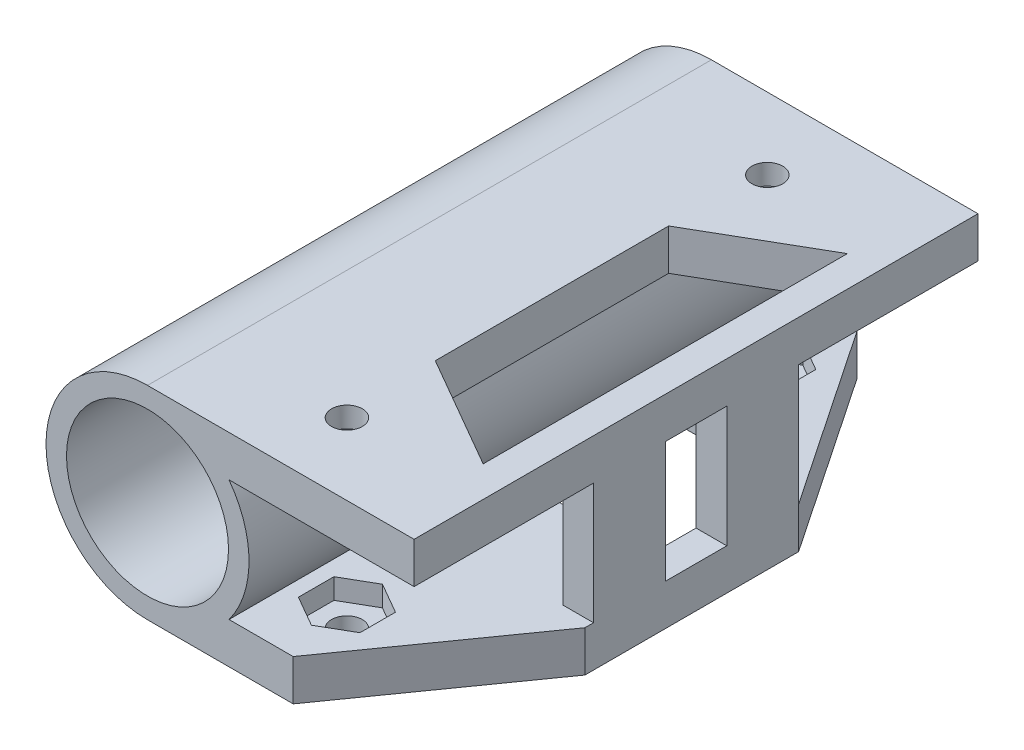
SolidWorks part; units mm, degrees
ref_plane "Спереди" through (0, 0, 0) normal (0, 0, 1) x (1, 0, 0)
ref_plane "Сверху" through (0, 0, 0) normal (0, 1, 0) x (1, 0, 0)
ref_plane "Справа" through (0, 0, 0) normal (1, 0, 0) x (0, 0, -1)
sketch "Эскиз2" plane through (0, 0, 0) normal (0, 0, 1) x (1, 0, 0)
  line L0 (0, 9.9) -> (26, 9.9)
  line L1 (26, 9.9) -> (26, 5.9)
  line L2 (26, 5.9) -> (7.9498, 5.9)
  line L3 (7.9498, -5.9) -> (26, -5.9)
  line L4 (0, -9.9) -> (26, -9.9)
  line L7 (26, -9.9) -> (26, -5.9)
  circle A0 centre (0, 0) radius 7.9
  circle A1 centre (0, 0) radius 9.9
  dimension "D2" = 15.8
  dimension "D3" = 19.8
  dimension "D1" = 4
  dimension "D4" = 26
  dimension "D5" = 4
  dimension "D6" = 26
extrude "Бобышка-Вытянуть1" add sketch "Эскиз2" against normal blind 7 and the other way blind 48 contours A1 A0 | A1 L2 L1 L0 | A1 L4 L7 L3 region at (15.6974, 8.0002, 0) region at (4.3239, 8.5935, 0) region at (15.6974, -8.0002, 0)
sketch "Эскиз3" plane through (0, 5.9, 0) normal (0, -1, 0) x (1, 0, 0)
  line L0 (26, -7) -> (7.9498, -7) construction
  line L1 (15.4498, -1.7321) -> (15.4498, 1.7321)
  line L2 (15.4498, 1.7321) -> (12.4498, 3.4641)
  line L3 (12.4498, 3.4641) -> (9.4498, 1.7321)
  line L4 (9.4498, 1.7321) -> (9.4498, -1.7321)
  line L5 (9.4498, -1.7321) -> (12.4498, -3.4641)
  line L6 (12.4498, -3.4641) -> (15.4498, -1.7321)
  line L7 (26, 20.5) -> (-7.1059, 20.5) construction
  line L8 (26, 48) -> (26, -7) construction
  line L9 (12.4498, 44.4641) -> (15.4498, 42.7321)
  line L10 (9.4498, 42.7321) -> (12.4498, 44.4641)
  line L11 (9.4498, 39.2679) -> (9.4498, 42.7321)
  line L12 (12.4498, 37.5359) -> (9.4498, 39.2679)
  line L13 (15.4498, 39.2679) -> (12.4498, 37.5359)
  line L14 (15.4498, 42.7321) -> (15.4498, 39.2679)
  circle A0 centre (12.4498, 0) radius 3 construction
  circle A1 centre (12.4498, 41) radius 3 construction
  dimension "D1" = 6
  dimension "D2" = 4.5
  dimension "D3" = 7
extrude "Вырез-Вытянуть1" cut sketch "Эскиз3" against normal blind 2
sketch "Эскиз4" plane through (0, 9.9, 0) normal (0, 1, 0) x (1, 0, 0)
  line L0 (26, -20.5) -> (0, -20.5) construction
  line L1 (26, -48) -> (26, 7) construction
  circle A0 centre (12.4498, 0) radius 1.5
  circle A1 centre (12.4498, -41) radius 1.5
  dimension "D1" = 3
extrude "Вырез-Вытянуть2" cut sketch "Эскиз4" against normal blind 28
sketch "Эскиз5" plane through (0, 9.9, 0) normal (0, 1, 0) x (1, 0, 0)
  line L0 (26, -1.0067) -> (11.9498, -9.1186)
  line L1 (26, -48) -> (26, 7) construction
  line L2 (11.9498, -9.1186) -> (11.9498, -31.8814)
  line L3 (11.9498, -31.8814) -> (26, -39.9933)
  line L4 (26, -39.9933) -> (26, -1.0067)
  line L5 (0, -48) -> (0, 7) construction
  line L6 (23, -2.7388) -> (23, -38.2612)
  line L7 (26, -48) -> (26, 7) construction
  point P4 (11.9498, -20.5)
  point P9 (0, -20.5)
  dimension "D1" = 120
  dimension "D2" = 120
  dimension "D3" = 4
  dimension "D4" = 3
extrude "Вырез-Вытянуть3" cut sketch "Эскиз5" against normal blind 10 contours L6 L0 L2 L3 region at (17.8781, 9.9, 20.5)
sketch "Эскиз7" plane through (0, 5.9, 0) normal (0, -1, 0) x (1, 0, 0)
  line L0 (23, 38.2612) -> (23, 2.7388) construction
  line L1 (23, 10.5) -> (26, 10.5)
  line L2 (23, 10.5) -> (23, 17.5)
  line L3 (23, 17.5) -> (26, 17.5)
  line L4 (26, 10.5) -> (26, 17.5)
  line L5 (26, 48) -> (26, -7) construction
  line L7 (23, 23.5) -> (26, 23.5)
  line L8 (23, 23.5) -> (23, 30.5)
  line L9 (23, 30.5) -> (26, 30.5)
  line L10 (26, 23.5) -> (26, 30.5)
  line L11 (23, 17.5) -> (26, 17.5)
  line L12 (23, 17.5) -> (23, 23.5)
  line L13 (23, 23.5) -> (26, 23.5)
  line L14 (26, 17.5) -> (26, 23.5)
  point P12 (23, 20.5)
  point P13 (23, 20.5)
  line M20 (26, -7) -> (26, 48)
  line M23 (23, 38.2612) -> (23, 2.7388)
  dimension "D1" = 7
  dimension "D2" = 7
  dimension "D3" = 6
extrude "Бобышка-Вытянуть3" add sketch "Эскиз7" along normal blind 12 contours L3 L1 M23 M20 | L9 L7 M23 M20 region at (24.5, 5.9, 14) region at (24.5, 5.9, 27)
sketch "Эскиз8" plane through (0, -9.9, 0) normal (0, -1, 0) x (1, 0, 0)
  line L0 (26, -7) -> (26, 10.5)
  line L1 (26, 48) -> (26, -7) construction
  line L2 (26, 10.5) -> (14.2078, -7)
  line L3 (0, -7) -> (26, -7) construction
  line L4 (14.2078, -7) -> (26, -7)
  line L5 (26, 48) -> (26, 31.3346)
  line L6 (26, 31.3346) -> (14.2078, 48)
  line L7 (0, 48) -> (26, 48) construction
  line L8 (14.2078, 48) -> (26, 48)
  line L9 (23, 10.5) -> (23, 2.7388) construction
  line L10 (23, 22) -> (9.9237, 22)
  line L11 (23, 22) -> (23, 11.61)
  line L12 (23, 11.61) -> (18.9758, 5.638)
  line L13 (9.9237, 22) -> (9.9237, 5.638)
  line L16 (18.9758, 5.638) -> (9.9237, 5.638)
  dimension "D1" = 29
extrude "Вырез-Вытянуть4" cut sketch "Эскиз8" against normal blind 10
extrude "Вырез-Вытянуть7" cut sketch "Эскиз3<2>" along normal blind 2 from surface contours L14 L9 L10 L11 L12 L13 | L5 L6 L1 L2 L3 L4 region at (12.4498, 5.9, 0) region at (12.4498, 5.9, 41) starting at face at (19.5077, -5.9, 19.1234)
sketch "Эскиз3<2>" plane through (0, 5.9, 0) normal (0, -1, 0) x (1, 0, 0) same geometry as "Эскиз3"
